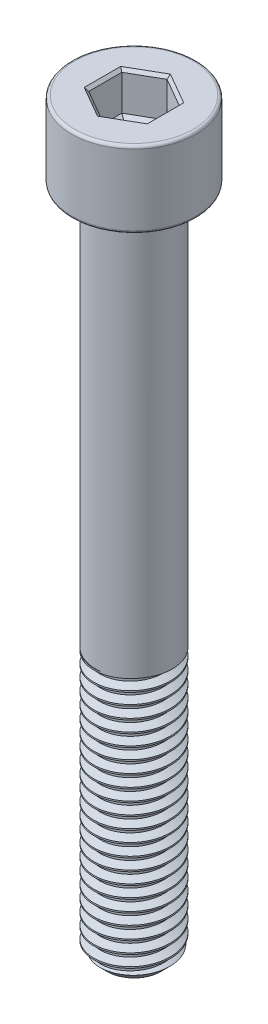
SolidWorks part; units mm, degrees
material "AISI Type A2 Tool Steel"
ref_plane "Front Plane" through (0, 0, 0) normal (0, 0, 1) x (1, 0, 0)
ref_plane "Top Plane" through (0, 0, 0) normal (0, 1, 0) x (1, 0, 0)
ref_plane "Right Plane" through (0, 0, 0) normal (1, 0, 0) x (0, 0, -1)
sketch "Sketch1" plane through (0, 0, 0) normal (0, 1, 0) x (1, 0, 0)
  circle A0 centre (0, 0) radius 4
  dimension "D1" = 8
extrude "Boss-Extrude1" add sketch "Sketch1" along normal blind 28
thread "Thread1" pitch 1.25 method cut profile "Thread Profile1" start angle 0, offset 2, length 0, pitch 1.25, diameter 8
ref_plane "Plane1" through (-4, 30, 0) normal (0, 0, 1) x (-1, 0, 0)
sketch "Thread Profile1" plane through (-4, 30, 0) normal (0, 0, 1) x (-1, 0, 0)
  line L0 (0, 0) -> (0, 1.25) construction
  line L11 (0, 0) -> (0, 1.0937)
  line L12 (0, 1.0937) -> (-0.6766, 0.7031)
  line L13 (-0.6766, 0.7031) -> (-0.6766, 0.3906)
  line L15 (-0.6766, 0.3906) -> (0, 0)
  line L17 (-0.6766, 0.5469) -> (0, 0.5469) construction
  point P2 (0, 0)
  dimension "Pitch" = 1.25
  dimension "Profile_Angle" = 60
  dimension "Profile_Land" = 0.3125
  dimension "Profile_Height" = 0.6766
sketch "Sketch2" plane through (0, 28, 0) normal (0, 1, 0) x (1, 0, 0)
  circle A0 centre (0, 0) radius 4
  dimension "D1" = 8
extrude "Boss-Extrude2" add sketch "Sketch2" along normal blind 42
sketch "Sketch5" plane through (0, 70, 0) normal (0, 1, 0) x (1, 0, 0)
  circle A0 centre (0, 0) radius 6.5
  dimension "D1" = 13
extrude "Boss-Extrude3" add sketch "Sketch5" along normal blind 8
sketch "Sketch6" plane through (0, 0, 0) normal (0, 0, 1) x (1, 0, 0)
  line L0 (0, 0) -> (0, 0.7245) construction
  line L1 (0, 0) -> (4.01, 0) construction
  line L2 (4.01, 0) -> (4.01, 1.2)
  line L3 (4.01, 1.2) -> (2.81, 0)
  line L4 (2.81, 0) -> (4.01, 0)
  dimension "D1" = 1.2
  dimension "D2" = 45
  dimension "D3" = 4.01
revolve "Cut-Revolve1" cut sketch "Sketch6" angle 360 about L0
fillet "Fillet1" radius 0.3 2 edges at (0, 70, 6.5) (0, 78, 6.5)
sketch "Sketch7" plane through (0, 78, 0) normal (0, 1, 0) x (1, 0, 0)
  line L1 (0, 3.4641) -> (-3, 1.7321)
  line L2 (-3, 1.7321) -> (-3, -1.7321)
  line L3 (-3, -1.7321) -> (0, -3.4641)
  line L4 (0, -3.4641) -> (3, -1.7321)
  line L5 (3, -1.7321) -> (3, 1.7321)
  line L6 (3, 1.7321) -> (0, 3.4641)
  circle A0 centre (0, 0) radius 3 construction
  dimension "D1" = 6
extrude "Cut-Extrude1" cut sketch "Sketch7" against normal blind 4
chamfer "Chamfer1" distance 0.3 angle 45 6 edges at (-3, 78, 0) (-1.5, 78, 2.5981) (1.5, 78, 2.5981) (3, 78, 0) (1.5, 78, -2.5981) (-1.5, 78, -2.5981)
sketch "Sketch8" plane through (0, 74, 0) normal (0, 1, 0) x (1, 0, 0)
  line L1 (0, 3.4641) -> (-3, 1.7321)
  line L2 (-3, 1.7321) -> (-3, -1.7321)
  line L3 (-3, -1.7321) -> (0, -3.4641)
  line L4 (0, -3.4641) -> (3, -1.7321)
  line L5 (3, -1.7321) -> (3, 1.7321)
  line L6 (3, 1.7321) -> (0, 3.4641)
  circle A0 centre (0, 0) radius 3 construction
extrude "Cut-Extrude2" cut sketch "Sketch8" against normal blind 0.4 draft 60
